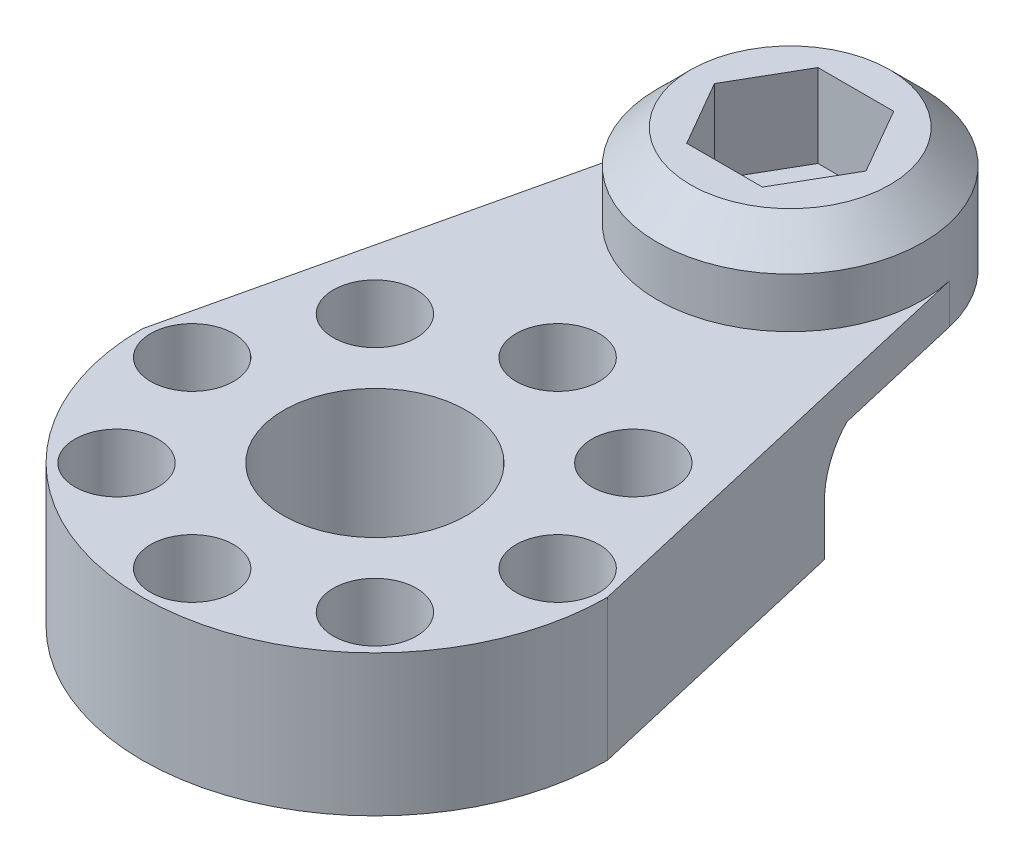
SolidWorks part; units mm, degrees
material "3003 Alloy"
ref_plane "Front Plane" through (0, 0, 0) normal (0, 0, 1) x (1, 0, 0)
ref_plane "Top Plane" through (0, 0, 0) normal (0, 1, 0) x (1, 0, 0)
ref_plane "Right Plane" through (0, 0, 0) normal (1, 0, 0) x (0, 0, -1)
sketch "Sketch1" plane through (0, 0, 0) normal (0, 1, 0) x (1, 0, 0)
  line L0 (0, 0) -> (0, 25) construction
  line L1 (-14, 0) -> (-14, 25)
  line L2 (14, 0) -> (14, 25)
  arc A0 (-14, 0) -> (14, 0) centre (0, 0) ccw
  arc A1 (14, 25) -> (-14, 25) centre (0, 25) ccw
  circle A2 centre (0, 25) radius 2
  circle A3 centre (0, 0) radius 5.5
  point P3 (0, 12.5)
  dimension "D3" = 11
  dimension "D4" = 4
  dimension "D1" = 25
  dimension "D2" = 28
extrude "Boss-Extrude1" add sketch "Sketch1" along normal blind 8.5
sketch "Sketch2" plane through (0, 8.5, 0) normal (0, 1, 0) x (1, 0, 0)
  line L0 (0, 0) -> (0, 11) construction
  circle A0 centre (0, 11) radius 1.55
  circle A1 centre (7.7782, 7.7782) radius 1.55
  circle A2 centre (11, 0) radius 1.55
  circle A3 centre (7.7782, -7.7782) radius 1.55
  circle A4 centre (0, -11) radius 1.55
  circle A5 centre (-7.7782, -7.7782) radius 1.55
  circle A6 centre (-11, 0) radius 1.55
  circle A7 centre (-7.7782, 7.7782) radius 1.55
  circle A8 centre (0, 0) radius 11 construction
  point P21 (0, 0)
  dimension "D1" = 3.1
  dimension "D2" = 11
  dimension "D3" = 8
extrude "Cut-Extrude1" cut sketch "Sketch2" against normal through all
sketch "Sketch3" plane through (0, 8.5, 0) normal (0, 1, 0) x (1, 0, 0)
  line L0 (-14, 0) -> (-7.7938, 26.8045)
  line L1 (14, 0) -> (7.7938, 26.8045)
  line L2 (-14, 25) -> (-14, 0) construction
  line L3 (14, 0) -> (14, 25) construction
  line L4 (-14, 25) -> (-14, 0)
  line L5 (14, 0) -> (14, 25)
  arc A1 (14, 25) -> (-14, 25) centre (0, 25) ccw construction
  circle A3 centre (0, 25) radius 8
  arc A4 (14, 25) -> (-14, 25) centre (0, 25) ccw
  line M12 (14, 0) -> (14, 25)
  arc M13 (14, 25) -> (-14, 25) centre (0, 25) ccw
  line M14 (-14, 25) -> (-14, 0)
  dimension "D1" = 16
extrude "Cut-Extrude2" cut sketch "Sketch3" against normal through all contours A3 L1 L0 M12 M13 M14 region at (-13.5199, 8.5, -12.5)
sketch "Croquis1" plane through (0, 8.5, 0) normal (0, 1, 0) x (1, 0, 0)
  line L1 (4.5611, 25) -> (2.2805, 28.95)
  line L2 (2.2805, 28.95) -> (-2.2805, 28.95)
  line L3 (-2.2805, 28.95) -> (-4.5611, 25)
  line L4 (-4.5611, 25) -> (-2.2805, 21.05)
  line L5 (-2.2805, 21.05) -> (2.2805, 21.05)
  line L6 (2.2805, 21.05) -> (4.5611, 25)
  circle A0 centre (0, 25) radius 3.95 construction
  circle A1 centre (0, 25) radius 8
  dimension "D1" = 7.9
extrude "Saliente-Extruir1" add sketch "Croquis1" along normal blind 5
chamfer "Chaflán1" distance 2 angle 45 1 edges at (0, 13.5, -17)
sketch "Croquis2" plane through (0, 0, 0) normal (0, -1, 0) x (-1, 0, 0)
  line L0 (-7.7938, 26.8045) -> (-10.0639, 17)
  line L1 (-14, 0) -> (-7.7938, 26.8045) construction
  line L2 (-10.0639, 17) -> (10.0639, 17)
  line L3 (14, 0) -> (7.7938, 26.8045) construction
  line L4 (10.0639, 17) -> (7.7938, 26.8045)
  arc A1 (-7.7938, 26.8045) -> (7.7938, 26.8045) centre (0, 25) cw
extrude "Cortar-Extruir1" cut sketch "Croquis2" against normal blind 6.1
sketch "Croquis3" plane through (-13.2877, 0, -3.0766) normal (-0.9742, 0, -0.2256) x (-0.2256, 0, 0.9742)
  line L0 (-14.2918, 6.1) -> (-24.3557, 6.1) construction
  line L1 (-14.2918, 6.1) -> (-14.2918, 0) construction
  line L3 (-19.3237, 7.4101) -> (-13.6045, 7.4101)
  line L4 (-13.6045, 7.4101) -> (-13.6045, 3.05)
  line L5 (-13.6045, 3.05) -> (-14.2918, 3.05)
  line L6 (-19.3237, 6.1) -> (-19.3237, 7.4101)
  arc A0 (-19.3237, 6.1) -> (-14.2918, 3.05) centre (-17.7097, 3.087) cw
extrude "Saliente-Extruir2" add sketch "Croquis3" along direction (-1, 0, 0) on the side against the normal up to surface (17.8577 mm away) up to face at (10.6192, 4.8667, -14.6015)
sketch "Croquis4" plane through (0, 8.5, 0) normal (0, 1, 0) x (1, 0, 0)
  circle A0 centre (0, 11) radius 2.5
  dimension "D1" = 5
extrude "Cortar-Extruir2" cut sketch "Croquis4" against normal blind 6
pattern_circular "MatrizC1" count 8 over 360 about axis through (0, 8.5, 0) along (0, 1, 0) of "Cortar-Extruir2"
sketch "Croquis5" plane through (0, 6.1, 0) normal (0, -1, 0) x (1, 0, 0)
  line L2 (0, -16.5742) -> (-8.1945, -25.0742)
  line L15 (-14, 0) -> (-7.7938, -26.8045) construction
  line L16 (0, -16.5742) -> (-10.1625, -16.5742)
  line L17 (-10.1625, -16.5742) -> (-8.1945, -25.0742)
  dimension "D1" = 8.5
extrude "Saliente-Extruir3" add sketch "Croquis5" along normal up to surface (6.1 mm away) up to face at (-7.7782, 0, -6.2282)
